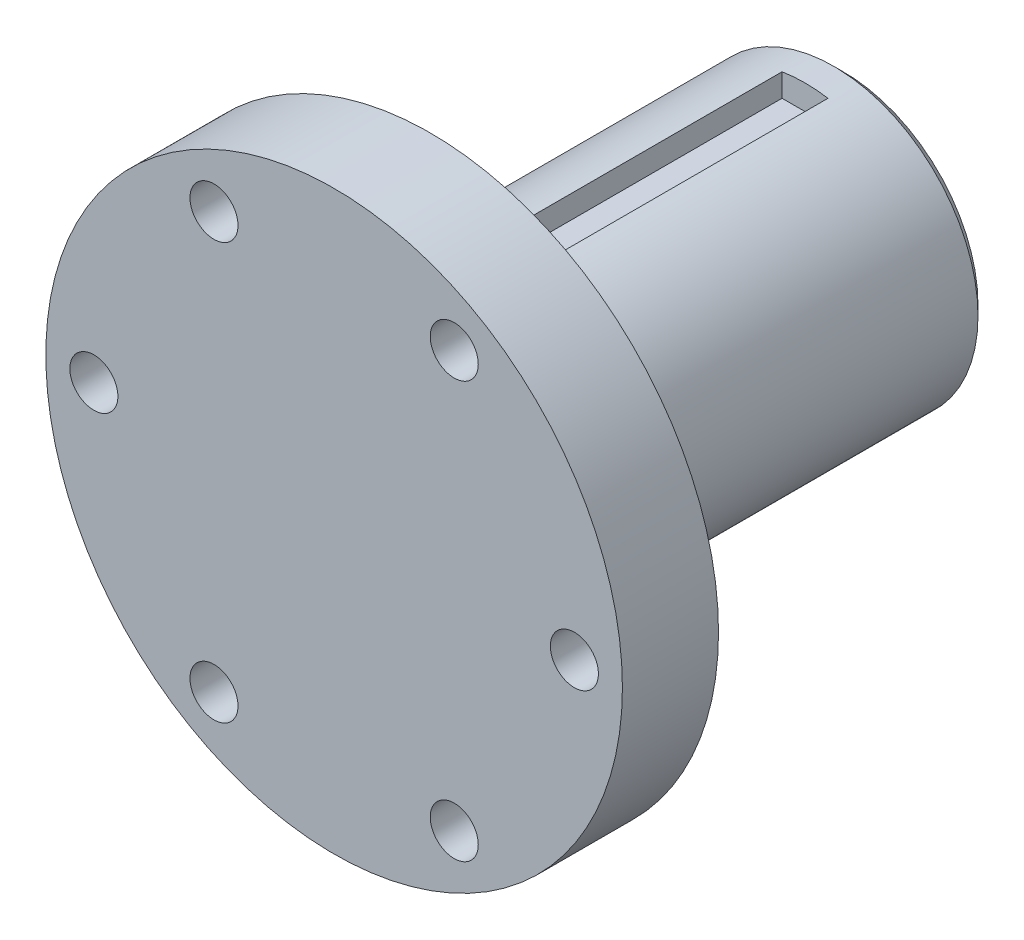
SolidWorks part; units mm, degrees
ref_plane "Płaszczyzna przednia" through (0, 0, 0) normal (0, 0, 1) x (1, 0, 0)
ref_plane "Płaszczyzna górna" through (0, 0, 0) normal (0, 1, 0) x (1, 0, 0)
ref_plane "Płaszczyzna prawa" through (0, 0, 0) normal (1, 0, 0) x (0, 0, -1)
sketch "Szkic1" plane through (0, 0, 0) normal (0, 0, 1) x (1, 0, 0)
  circle A0 centre (0, 0) radius 15
  dimension "D1" = 30
extrude "Dodanie-wyciągnięcie1" add sketch "Szkic1" along normal blind 53 contours A0
ref_plane "Płaszczyzna1" through (0, 0, 4) normal (0, 0, -1) x (-1, 0, 0)
chamfer "Sfazowanie1" distance 1 angle 45 1 edges at (15, 0, 0)
sketch "Szkic2" plane through (0, 0, 4) normal (0, 0, -1) x (-1, 0, 0)
  line L0 (-2.39, 14.8084) -> (-2.39, 12.4184)
  line L1 (-2.39, 12.4184) -> (2.39, 12.4184)
  line L2 (2.39, 12.4184) -> (2.39, 14.8084)
  circle A0 centre (0, 0) radius 15 construction
  arc A1 (2.39, 14.8084) -> (-2.39, 14.8084) centre (0, 0) ccw
  point P5 (0, 12.4184)
  dimension "D1" = 4.78
  dimension "D2" = 2.39
extrude "Wytnij-wyciągnięcie1" cut sketch "Szkic2" against normal blind 35
sketch "Szkic3" plane through (0, 0, 53) normal (0, 0, 1) x (1, 0, 0)
  circle A0 centre (0, 0) radius 30
  dimension "D1" = 60
extrude "Dodanie-wyciągnięcie2" add sketch "Szkic3" against normal blind 10
sketch "Szkic4" plane through (0, 0, 43) normal (0, 0, -1) x (-1, 0, 0)
  circle A0 centre (-25, 0) radius 2.5
  dimension "D1" = 5
  dimension "D2" = 25
extrude "Wytnij-wyciągnięcie2" cut sketch "Szkic4" against normal through all
pattern_circular "Szyk kołowy1" count 6 over 360 about axis through (0, 0, 43) along (0, 0, 1) of "Wytnij-wyciągnięcie2"
